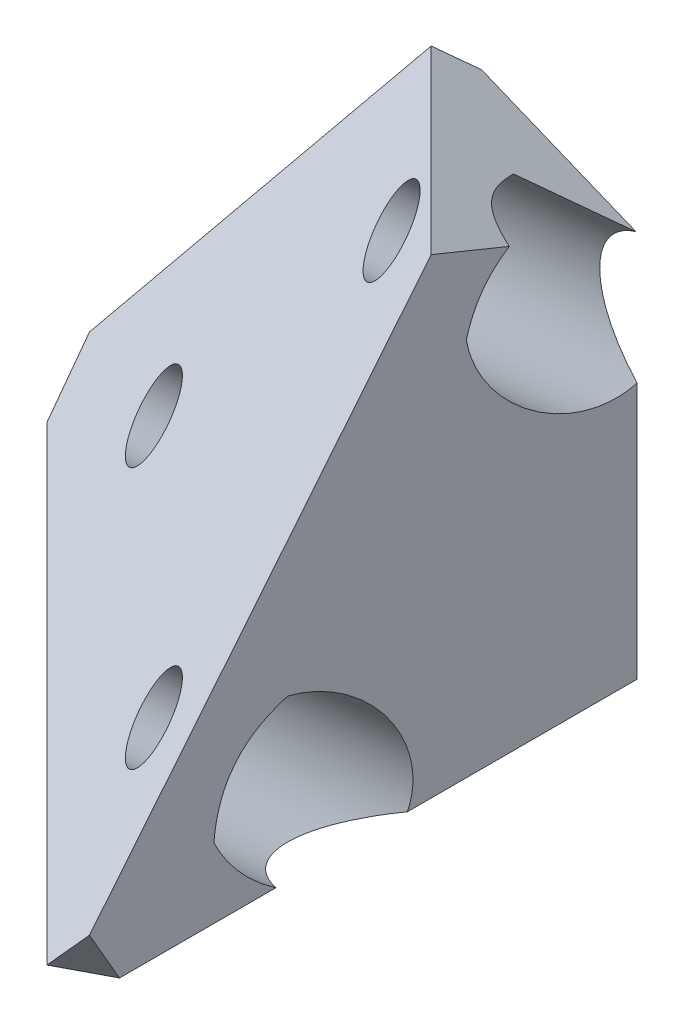
SolidWorks part; units mm, degrees
ref_plane "Front Plane" through (0, 0, 0) normal (0, 0, 1) x (1, 0, 0)
ref_plane "Top Plane" through (0, 0, 0) normal (0, 1, 0) x (1, 0, 0)
ref_plane "Right Plane" through (0, 0, 0) normal (1, 0, 0) x (0, 0, -1)
sketch "Sketch1" plane through (0, 0, 0) normal (0, 1, 0) x (1, 0, 0)
  line L0 (-7.7782, 7.7782) -> (7.7782, -7.7782)
  line L1 (-7.7782, 7.7782) -> (7.7782, 7.7782)
  line L2 (7.7782, 7.7782) -> (7.7782, -7.7782)
  dimension "D1" = 22
extrude "Boss-Extrude1" add sketch "Sketch1" along normal blind 14
ref_plane "Plane1" through (0, 0, 0) normal (-0.7071, 0, -0.7071) x (0, -1, 0)
sketch "Sketch2" plane through (0, 0, 0) normal (-0.7071, 0, -0.7071) x (0, -1, 0)
  line L0 (0, 0) -> (-14, -8.0829)
  line L1 (-14, -8.0829) -> (-14, 0)
  line L2 (-14, 0) -> (0, 0)
  point P3 (0, 0)
  dimension "D1" = 30
extrude "Cut-Extrude1" cut sketch "Sketch2" against normal through all both and the other way through all
ref_plane "Plane2" through (7.3485, -6, -7.3485) normal (-0.6124, 0.5, 0.6124) x (0.7906, 0.3873, 0.4743)
sketch "Sketch7" plane through (0, 0, -7.7782) normal (0, 0, -1) x (-1, 0, 0)
  line L4 (-7.7782, 0) -> (7.7782, 0)
  line L5 (7.7782, 0) -> (-3.6528, 14)
  line L6 (-3.6528, 14) -> (-7.7782, 14)
  line L7 (-7.7782, 14) -> (-7.7782, 0)
  line L8 (-7.7782, 0) -> (7.7782, 0)
  line L9 (7.7782, 0) -> (-3.6528, 14)
  line L10 (-3.6528, 14) -> (-7.7782, 14)
  line L11 (-7.7782, 14) -> (-7.7782, 0)
  dimension "D1" = 0
extrude "Boss-Extrude2" add sketch "Sketch7" along normal blind 2
hole_wizard "CSK for M2 Flat Head Machine Screw1" positions "Sketch3" profile "Sketch4" countersink size "M2" standard "ANSI Metric"
sketch "Sketch3" plane through (7.3485, -6, -7.3485) normal (-0.6124, 0.5, 0.6124) x (0.7906, 0.3873, 0.4743)
  line L1 (7.2296, 14.4591) -> (2.4597, 4.9193) construction
  line L2 (6.9318, 1.5652) -> (-2.9069, 6.4846) construction
  line L4 (-9.8387, 4.9193) -> (9.8387, -4.9193) construction
  line L5 (9.8387, 13.1546) -> (4.6204, 15.7637) construction
  point P0 (6.9318, 1.5652)
  point P4 (6.4846, 12.9692)
  point P12 (-2.9069, 6.4846)
  point P21 (0, 0)
  point P22 (0, 0)
  dimension "D1" = 5.5
  dimension "D2" = 10
  dimension "D3" = 4.5
sketch "Sketch4" plane through (12.8285, -2.1029, -5.0504) normal (0.7891, 0.4344, 0.4344) x (-0.0488, 0.7492, -0.6605)
  line L0 (0, 0) -> (0, 13.921)
  line L1 (0, 13.921) -> (1.2, 13.2)
  line L2 (1.2, 13.2) -> (1.2, 11)
  line L3 (1.2, 11) -> (2.2, 10)
  line L4 (2.2, 10) -> (2.2, 0)
  line L6 (2.2, 0) -> (0, 0)
  line L7 (-1.2, 11) -> (-2.2, 10) construction
  line L10 (0, 13.921) -> (-1.2, 13.2) construction
  line L11 (0, -6.35) -> (0, 107.95) construction
  dimension "Hole Dia." = 2.4
  dimension "Hole Depth" = 13.2
  dimension "C'Sink Dia." = 4.4
  dimension "C'Sink Angle" = 90
  dimension "Drill Angle" = 118
  dimension "Head Clearance" = 10
hole_wizard "M2x0.4 Tapped Hole1" positions "Sketch5" profile "Sketch6" tap size "M2x0.4" standard "ANSI Metric"
sketch "Sketch5" plane through (0, 0, -9.7782) normal (0, 0, -1) x (-1, 0, 0)
  line L2 (-7.7782, 7.6299) -> (-7.7782, 0) construction
  line L3 (0.5668, 0) -> (7.7782, 0) construction
  point P0 (-2.7782, 9.5)
  point P2 (-5.7782, 1.5)
  point P4 (3.7218, 1.5)
  point P7 (0, 0)
  point P16 (-6.9111, 0.5937)
  point P23 (6.1794, -0.2251)
  dimension "D1" = 1.5
  dimension "D2" = 2
  dimension "D3" = 8
  dimension "D4" = 3
  dimension "D5" = 9.5
sketch "Sketch6" plane through (2.7782, 9.5, -9.7782) normal (1, 0, 0) x (0, 1, 0)
  line L0 (0, 0) -> (0, 3.9807)
  line L1 (0, 3.9807) -> (0.8, 3.5)
  line L2 (0.8, 3.5) -> (0.8, 0.225)
  line L3 (0.8, 0.225) -> (1.025, 0)
  line L5 (1.025, 0) -> (0, 0)
  line L6 (-0.8, 0.225) -> (-1.025, 0) construction
  line L10 (0, 3.9807) -> (-0.8, 3.5) construction
  line L11 (0, -6.35) -> (0, 107.95) construction
  dimension "Tap Drill Dia." = 1.6
  dimension "Tap Drill Depth" = 3.5
  dimension "Near C'Sink Dia." = 2.05
  dimension "Near C'Sink Angle" = 90
  dimension "Drill Angle" = 118
cosmetic thread "Hole Thread1" parameters "D1"=3, "D2"=2
cosmetic thread "Hole Thread3" parameters "D1"=3, "D2"=2
cosmetic thread "Hole Thread4" parameters "D1"=3, "D2"=2
sketch "Sketch11" plane through (0, 0, 0) normal (-0.6124, 0.5, 0.6124) x (0.4743, -0.3873, 0.7906)
  line L4 (-4.6204, 15.7637) -> (-9.463, 15.7637)
  line L5 (-9.463, 15.7637) -> (-11.4198, 13.1546)
  line L6 (-11.4198, 13.1546) -> (-9.8387, 13.1546)
  line L7 (-9.8387, 13.1546) -> (-4.6204, 15.7637)
  line L8 (-4.6204, 15.7637) -> (-9.463, 15.7637)
  line L9 (-9.463, 15.7637) -> (-11.4198, 13.1546)
  line L10 (-11.4198, 13.1546) -> (-9.8387, 13.1546)
  line L11 (-9.8387, 13.1546) -> (-4.6204, 15.7637)
  dimension "D1" = 0
extrude "Boss-Extrude4" [suppressed] add sketch "Sketch11" against normal up to surface (1.2247 mm away) up to face at (5.7155, 14, -7.7468)
sketch "Sketch12" plane through (0, 0, 0) normal (-0.6124, 0.5, 0.6124) x (0.4743, -0.3873, 0.7906)
  line L4 (-9.8387, -4.9193) -> (-9.8387, 13.1546)
  line L5 (-9.8387, 13.1546) -> (-11.4198, 13.1546)
  line L6 (-11.4198, 13.1546) -> (-11.4198, -4.9193)
  line L7 (-11.4198, -4.9193) -> (-9.8387, -4.9193)
  line L8 (-9.8387, -4.9193) -> (-9.8387, 13.1546)
  line L9 (-9.8387, 13.1546) -> (-11.4198, 13.1546)
  line L10 (-11.4198, 13.1546) -> (-11.4198, -4.9193)
  line L11 (-11.4198, -4.9193) -> (-9.8387, -4.9193)
  dimension "D1" = 0
extrude "Boss-Extrude5" add sketch "Sketch12" against normal up to surface (1.2247 mm away) up to face at (-2.0627, 7, -8.7782)
sketch "Sketch9" plane through (0, 0, 0) normal (-0.6124, 0.5, 0.6124) x (0.4743, -0.3873, 0.7906)
  line L0 (8.2387, 6.1193) -> (8.0498, 4.0249)
  line L1 (-4.6204, 15.7637) -> (9.8387, 4.9193) construction
  line L2 (-9.8387, -4.9193) -> (9.8387, 4.9193) construction
  line L3 (8.0498, 4.0249) -> (9.8387, 4.9193)
  line L4 (9.8387, 4.9193) -> (8.2387, 6.1193)
  line L5 (-9.631, -4.8155) -> (-11.4198, -5.7099)
  line L6 (-11.4198, -5.7099) -> (-11.4198, -3.7099)
  line L7 (-11.4198, -3.7099) -> (-9.631, -4.8155)
  line L8 (-9.631, -4.8155) -> (-9.9137, -4.963)
  line L10 (-11.4198, 13.1546) -> (-11.4198, -4.9193) construction
  line L11 (-4.6204, 15.7637) -> (-11.4198, 12.364)
  line L12 (-11.4198, 12.364) -> (-11.4198, 20.8633)
  line L13 (-11.4198, 20.8633) -> (-4.6204, 15.7637)
  line L14 (-4.6204, 15.7637) -> (-9.8387, 13.1546) construction
  dimension "D1" = 2
extrude "Cut-Extrude3" cut sketch "Sketch9" against normal through all both and the other way through all contours L5 L6 L7 | L0 L3 L4 | L12 L13 L11
